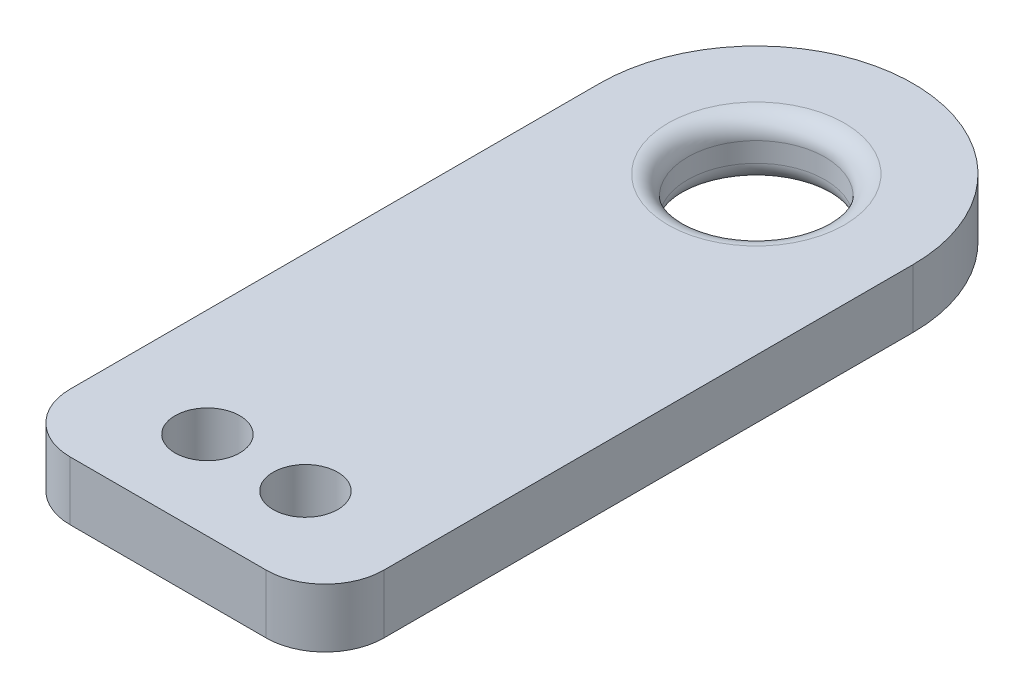
SolidWorks part; units mm, degrees
ref_plane "Plano frontal" through (0, 0, 0) normal (0, 0, 1) x (1, 0, 0)
ref_plane "Plano superior" through (0, 0, 0) normal (0, 1, 0) x (1, 0, 0)
ref_plane "Plano direito" through (0, 0, 0) normal (1, 0, 0) x (0, 0, -1)
sketch "Sketch2" plane through (0, 0, 0) normal (0, 1, 0) x (1, 0, 0)
  circle A0 centre (0, 0) radius 8
  dimension "D1" = 16
extrude "Boss-Extrude1" add sketch "Sketch2" against normal blind 1.5 and the other way blind 1.5
sketch "Sketch3" plane through (0, 0, 0) normal (0, 1, 0) x (1, 0, 0)
  line L1 (-8, 0) -> (8, 0)
  line L2 (-8, 0) -> (-8, -30)
  line L3 (-8, -30) -> (8, -30)
  line L4 (8, 0) -> (8, -30)
  circle A0 centre (0, 0) radius 8 construction
  point P6 (0, 0)
  point P7 (8, 0)
  dimension "D1" = 30
extrude "Boss-Extrude2" add sketch "Sketch3" along normal mid plane 3
sketch "Sketch4" plane through (0, 1.5, 0) normal (0, 1, 0) x (1, 0, 0)
  line L0 (-8, -30) -> (8, -30) construction
  circle A0 centre (2.5, -25.5) radius 1.65
  circle A1 centre (-2.5, -25.5) radius 1.65
  point P6 (0, 0)
  point P8 (4.4561, -27.0408)
  dimension "D1" = 3.3
  dimension "D2" = 3.3
  dimension "D3" = 4.5
  dimension "D4" = 2.5
  dimension "D5" = 2.5
extrude "Cut-Extrude1" cut sketch "Sketch4" against normal up to next
sketch "Sketch5" plane through (0, -1.5, 0) normal (0, -1, 0) x (1, 0, 0)
  circle A0 centre (0, 0) radius 3.5
  dimension "D1" = 7
extrude "Cut-Extrude2" cut sketch "Sketch5" against normal up to next
fillet "Fillet1" radius 1 2 edges at (0, 1.5, 3.5) (0, -1.5, -3.5)
fillet "Fillet2" radius 3 2 edges at (-8, 0, 30) (8, 0, 30)
equation "\"D2@Sketch4\"=\"D1@Sketch4\""
equation "\"D5@Sketch4\"=\"D4@Sketch4\""
